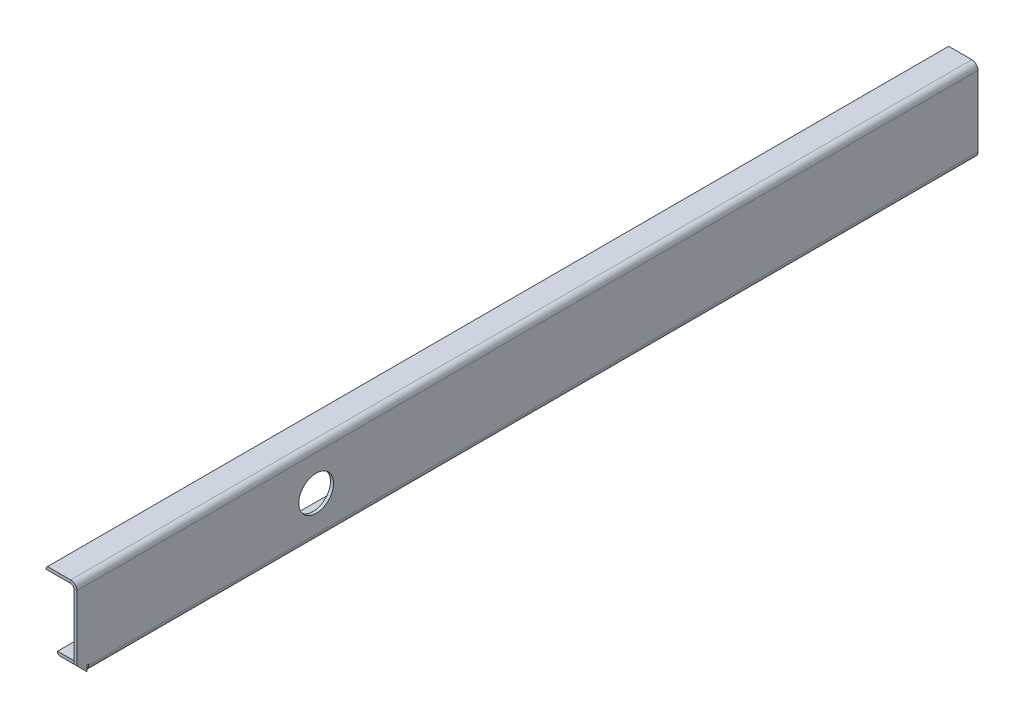
SolidWorks part; units mm, degrees
note: The reader was unsure of these and kept them because the rebuilt part matched: flange length of "边线-法兰1"; thickness of "边线-法兰1".
material "Q460"
ref_plane "前视基准面" through (0, 0, 0) normal (0, 0, 1) x (1, 0, 0)
ref_plane "上视基准面" through (0, 0, 0) normal (0, 1, 0) x (1, 0, 0)
ref_plane "右视基准面" through (0, 0, 0) normal (1, 0, 0) x (0, 0, -1)
sketch "草图1" plane through (0, 0, 0) normal (1, 0, 0) x (0, 0, -1)
  line L0 (0, 0) -> (2335, 0)
  line L1 (2335, 0) -> (2335, -215)
  line L2 (2335, -215) -> (30, -215)
  line L3 (30, -215) -> (0, -185)
  line L4 (0, -185) -> (0, 0)
  dimension "D1" = 215
  dimension "D2" = 30
  dimension "D3" = 30
  dimension "D4" = 2335
base flange "基体-法兰1" sketch "草图1" thickness 8 reverse thickness direction no parameters "D1"=5
edge flange "边线-法兰1" sketch "草图10" flange profiles "草图10", "草图11" flange angle 90 flange length 80 flange position material inside bend radius 8 thickness 8 relief rectangular parameters "D6"=10, "D8"=1
sketch "草图10" plane through (-8, 0, 0) normal (0, -1, 0) x (0, 0, 1)
  line L2 (-2335, 0) -> (-2335, 72)
  line L3 (-2335, 72) -> (0, 72)
  line L4 (0, 72) -> (0, 0)
  line L5 (0, 0) -> (-2335, 0) construction
  line L6 (0, 0) -> (-2335, 0)
sketch "草图11" plane through (-8, -215, 0) normal (0, 1, 0) x (0, 0, -1)
  line L0 (2335, 0) -> (30, 0) construction
  line L1 (2335, 0) -> (30, 0)
  line L2 (2335, 0) -> (2335, 72)
  line L3 (2335, 72) -> (30, 72)
  line L4 (30, 72) -> (30, 0)
bend "边线折弯1" bend radius 8 bend angle 90 parameters "D5"=1
bend "边线折弯2" bend radius 8 bend angle 90 parameters "D5"=2
chamfer "倒角1" distance 4 angle 45 2 edges at (-80, -215, -1182.5) (-80, 0, -1167.5)
sketch "草图12" plane through (0, 0, 0) normal (1, 0, 0) x (0, 0, -1)
  line L0 (0, 0) -> (2335, 0) construction
  line L1 (0, -16) -> (0, -185) construction
  circle A0 centre (620, -107.5) radius 45
  dimension "D1" = 90
  dimension "D2" = 107.5
  dimension "D3" = 620
extrude "切除-拉伸1" cut sketch "草图12" against normal through all normal cut yes
sketch "折弯-线1" [suppressed] plane through (0, 0, 0) normal (0, 1, 0) x (1, 0, 0)
sketch "边界框1" [suppressed] plane through (0, 0, 0) normal (0, 1, 0) x (1, 0, 0)
sheet metal parameters "钣金6" thickness 8 parameters "D1"=5
flat pattern "平板型式6" [suppressed]
sketch "折弯-线2" plane through (0, 0, 0) normal (0, 1, 0) x (1, 0, 0)
sketch "边界框2" [suppressed] plane through (0, 0, 0) normal (0, 1, 0) x (1, 0, 0)
sheet metal parameters "钣金7" thickness 8 parameters "D1"=5, "D7"=86
flat pattern "平板型式6" [suppressed]
sketch "折弯-线2" plane through (0, 0, 0) normal (0, 1, 0) x (1, 0, 0)
sketch "边界框2" [suppressed] plane through (0, 0, 0) normal (0, 1, 0) x (1, 0, 0)
bend of the flat pattern "展开-<边线折弯1>1"
bend of the flat pattern "展开-<边线折弯2>1"
sheet metal parameters "钣金10" thickness 8 parameters "D1"=5, "D7"=86
flat pattern "平板型式6"
sketch "折弯-线2" plane through (0, 0, 0) normal (1, 0, 0) x (0, 0, -1)
  line L0 (30, -208.4248) -> (2335, -208.4248) construction
  line L1 (2335, -6.5752) -> (0, -6.5752) construction
  line L2 (30, -208.4248) -> (2335, -208.4248) construction
  line L3 (2335, -6.5752) -> (0, -6.5752) construction
sketch3d "边界框2" [suppressed]
  line L0 (2335, -281.8496, -8) -> (0, -281.8496, -8) construction
  line L1 (2335, 66.8496, -8) -> (0, 66.8496, -8) construction
  line L2 (2335, -281.8496, -8) -> (2335, 66.8496, -8) construction
  line L3 (0, -281.8496, -8) -> (0, 66.8496, -8) construction
bend of the flat pattern "展开-<边线折弯1>1"
bend of the flat pattern "展开-<边线折弯2>1"
